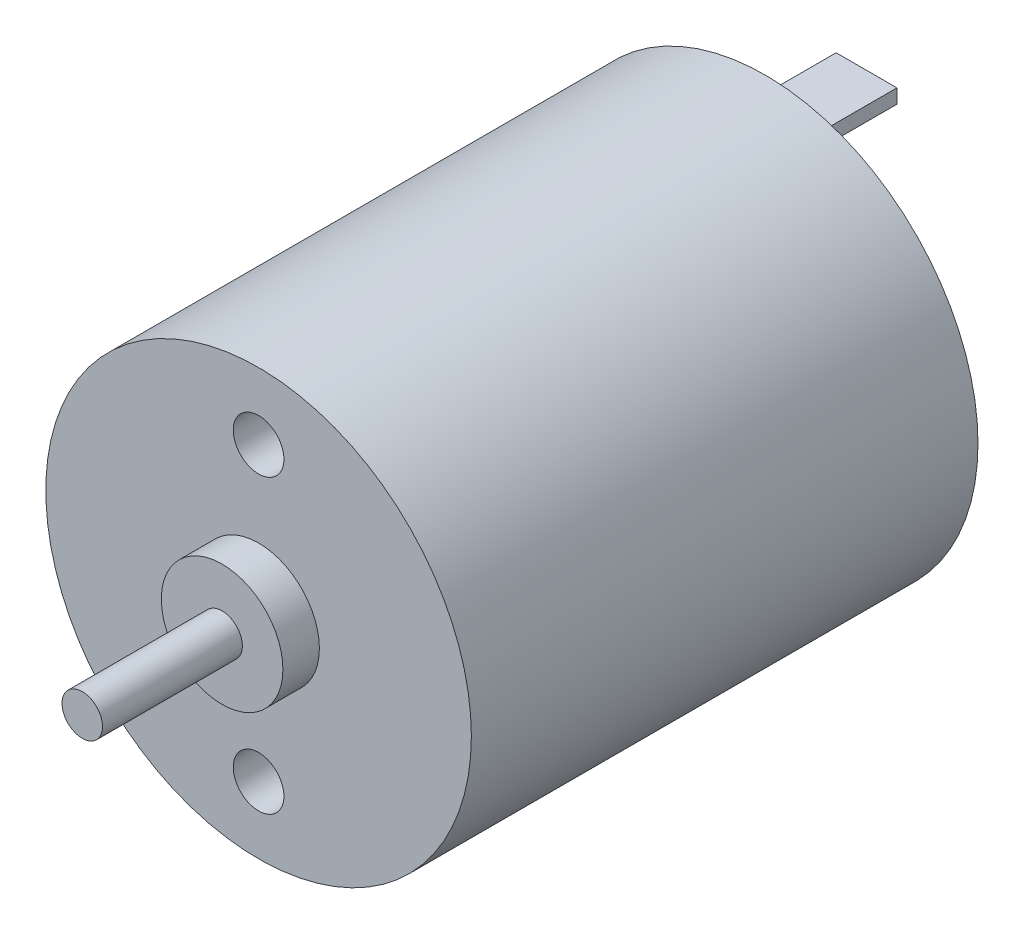
SolidWorks part; units mm, degrees
ref_plane "前视基准面" through (0, 0, 0) normal (0, 0, 1) x (1, 0, 0)
ref_plane "上视基准面" through (0, 0, 0) normal (0, 1, 0) x (1, 0, 0)
ref_plane "右视基准面" through (0, 0, 0) normal (1, 0, 0) x (0, 0, -1)
other "Configuration Table"
sketch "草图1" plane through (0, 0, 0) normal (0, 0, 1) x (1, 0, 0)
  line L12 (15.95, 15.99) -> (15.95, -15.1175) construction
  line L22 (-3.5, 5.9995) -> (-3.5, -4.0704) construction
  line L23 (4.5, 6.4068) -> (4.5, 4.4679) construction
  circle A11 centre (0, 0) radius 10.5
  dimension "D1" = 21
extrude "凸台-拉伸1" add sketch "草图1" along normal blind 25
sketch "草图2" plane through (0, 0, 25) normal (0, 0, 1) x (1, 0, 0)
  circle A0 centre (0, 0) radius 3
  dimension "D1" = 6
extrude "凸台-拉伸2" add sketch "草图2" along normal blind 1.8
sketch "草图3" plane through (0, 0, 26.8) normal (0, 0, 1) x (1, 0, 0)
  circle A0 centre (0, 0) radius 1
  dimension "D1" = 2
extrude "凸台-拉伸3" add sketch "草图3" along normal blind 8.7 from surface starting at face at (3, 0, 25)
extrude "凸台-拉伸4" add sketch "草图2<2>" against normal blind 2.6 from surface starting at face at (10.5, 0, 0)
sketch "草图2<2>" plane through (0, 0, 25) normal (0, 0, 1) x (1, 0, 0) same geometry as "草图2"
sketch "草图4" plane through (0, 0, 0) normal (0, 0, -1) x (-1, 0, 0)
  line L0 (0, 8.2) -> (0, -8.2) construction
  line L1 (-1.5, 8.2) -> (1.5, 8.2)
  line L2 (-1.5, 8.2) -> (-1.5, 7.5)
  line L3 (-1.5, 7.5) -> (1.5, 7.5)
  line L4 (1.5, 8.2) -> (1.5, 7.5)
  line L5 (-1.5, -7.5) -> (1.5, -7.5)
  line L6 (-1.5, -7.5) -> (-1.5, -8.2)
  line L7 (-1.5, -8.2) -> (1.5, -8.2)
  line L8 (1.5, -7.5) -> (1.5, -8.2)
  dimension "D1" = 16.4
  dimension "D2" = 3
  dimension "D3" = 0.7
extrude "凸台-拉伸5" add sketch "草图4" along normal blind 5
sketch "草图5" plane through (0, 0, 25) normal (0, 0, 1) x (1, 0, 0)
  line L0 (0, 7.2) -> (0, -7.2) construction
  line L1 (-5.4358, 5.95) -> (7.3996, 5.95) construction
  line L2 (-4.1188, -5.95) -> (7.1906, -5.95) construction
  circle A0 centre (0, 7.2) radius 1.25
  circle A1 centre (0, -7.2) radius 1.25
  dimension "D1" = 2.5
  dimension "D2" = 11.9
extrude "切除-拉伸1" cut sketch "草图5" against normal blind 5
